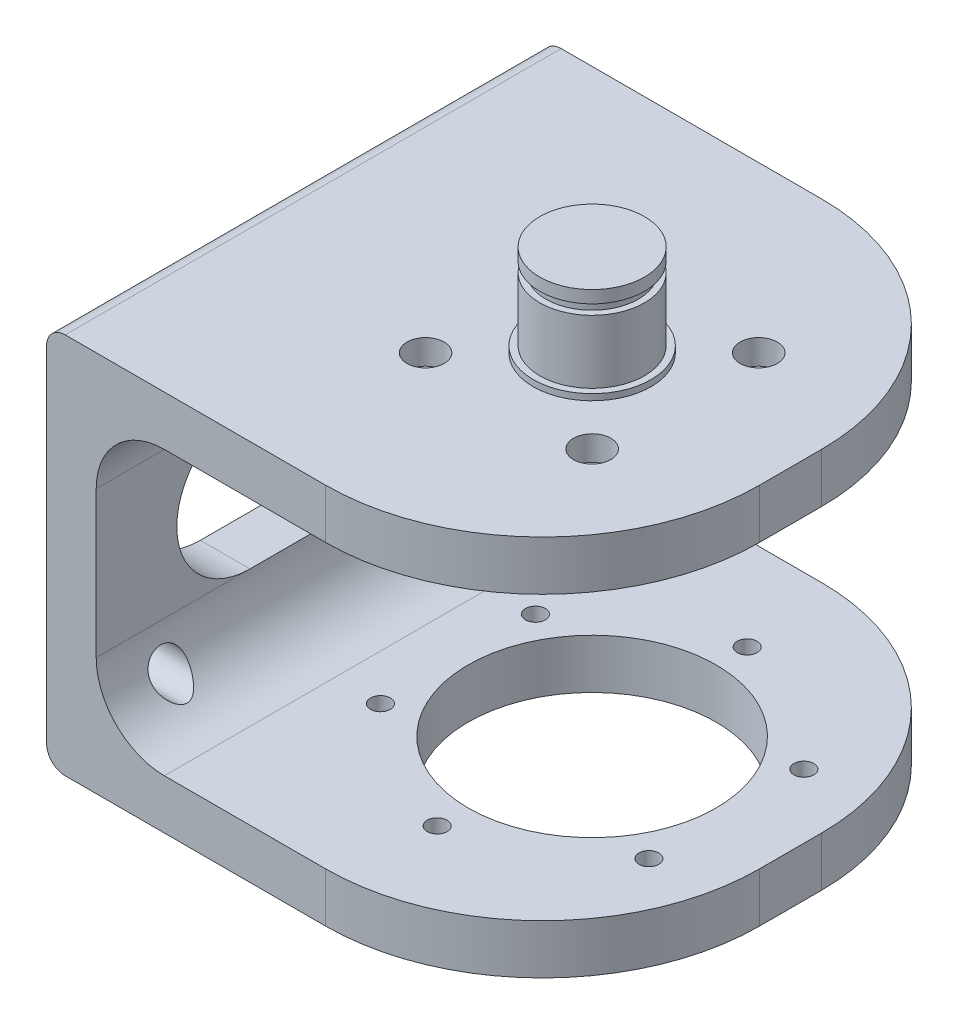
SolidWorks part; units mm, degrees
material "PETG-CF"
ref_plane "Front Plane" through (0, 0, 0) normal (0, 0, 1) x (1, 0, 0)
ref_plane "Top Plane" through (0, 0, 0) normal (0, 1, 0) x (1, 0, 0)
ref_plane "Right Plane" through (0, 0, 0) normal (1, 0, 0) x (0, 0, -1)
sketch "草图1" plane through (0, 0, 0) normal (0, 1, 0) x (1, 0, 0)
  line L1 (40, -40) -> (-40, -40)
  line L2 (40, -40) -> (40, 40)
  line L3 (40, 40) -> (-40, 40)
  line L4 (-40, -40) -> (-40, 40)
  line L5 (40, -40) -> (-40, 40) construction
  line L6 (40, 40) -> (-40, -40) construction
  point P0 (0, 0)
  dimension "D1" = 80
  dimension "D2" = 80
extrude "凸台-拉伸1" add sketch "草图1" along normal blind 8
sketch "草图2" plane through (0, 8, 0) normal (0, 1, 0) x (1, 0, 0)
  line L0 (-40, -40) -> (40, -40) construction
  line L1 (-32, -40) -> (-40, -40)
  line L2 (-32, -40) -> (-32, 40)
  line L3 (-32, 40) -> (-40, 40)
  line L4 (-40, -40) -> (-40, 40)
  line L5 (-32, -40) -> (-40, 40) construction
  line L6 (-32, 40) -> (-40, -40) construction
  point P0 (-36, 0)
  dimension "D1" = 8
extrude "凸台-拉伸2" add sketch "草图2" along normal blind 53.6
sketch "草图5" plane through (-32, 0, 0) normal (1, 0, 0) x (0, 0, -1)
  line L0 (-40, 61.6) -> (-40, 8) construction
  line L1 (40, 53.6) -> (-40, 53.6)
  line L2 (40, 53.6) -> (40, 61.6)
  line L3 (40, 61.6) -> (-40, 61.6)
  line L4 (-40, 53.6) -> (-40, 61.6)
  line L5 (40, 53.6) -> (-40, 61.6) construction
  line L6 (40, 61.6) -> (-40, 53.6) construction
  line L7 (40, 61.6) -> (40, 8) construction
  line L9 (-40, 61.6) -> (40, 61.6) construction
  point P0 (0, 57.6)
  dimension "D1" = 8
extrude "凸台-拉伸3" add sketch "草图5" along normal through all
sketch "草图4" plane through (0, 8, 0) normal (0, 1, 0) x (1, 0, 0)
  line L0 (-40, 40) -> (-40, -40) construction
  line L2 (40, -40) -> (40, 40) construction
  circle A0 centre (8, 0) radius 25 construction
  circle A1 centre (8, 25) radius 1.6
  circle A2 centre (-13.6506, 12.5) radius 1.6
  circle A3 centre (-13.6506, -12.5) radius 1.6
  circle A4 centre (8, -25) radius 1.6
  circle A5 centre (8, 0) radius 20
  circle A6 centre (29.6506, -12.5) radius 1.6
  circle A7 centre (29.6506, 12.5) radius 1.6
  point P17 (8, 0)
  point P22 (-40, 0)
  dimension "D3" = 50
  dimension "D4" = 3.2
  dimension "D6" = 40
  dimension "D1" = 32
  dimension "D5" = 6
extrude "切除-拉伸1" cut sketch "草图4" against normal through all contours A5 | A2 | A1 | A4 | A3 | A7 | A6
sketch "草图7" plane through (0, 61.6, 0) normal (0, 1, 0) x (1, 0, 0)
  line L0 (40, 40) -> (40, -40) construction
  line L3 (8, 0) -> (-5.435, 13.435) construction
  line L4 (8, 0) -> (8, 19) construction
  circle A0 centre (8, 0) radius 19 construction
  circle A5 centre (-5.435, 13.435) radius 1.6
  circle A6 centre (21.435, 13.435) radius 1.6
  circle A7 centre (21.435, -13.435) radius 1.6
  circle A8 centre (-5.435, -13.435) radius 1.6
  point P2 (5, 0)
  point P5 (5, 0)
  point P6 (10.7834, -6.382)
  point P10 (40, 0)
  point P20 (8, 0)
  dimension "D1" = 38
  dimension "D4" = 45
  dimension "D5" = 3.2
  dimension "D6" = 4
extrude "切除-拉伸3" cut sketch "草图7" against normal up to next
fillet "圆角3" radius 35 4 edges at (40, 4, 40) (40, 4, -40) (40, 57.6, -40) (40, 57.6, 40)
fillet "圆角4" radius 11 2 edges at (-32, 8, 0) (-32, 53.6, 0)
fillet "圆角5" radius 3 2 edges at (-40, 0, 0) (-40, 61.6, 0)
sketch "草图6" plane through (-40, 0, 0) normal (-1, 0, 0) x (0, 0, 1)
  line L0 (-40, 61.6) -> (40, 61.6) construction
  line L1 (30, 13) -> (-30, 13) construction
  line L2 (30, 13) -> (30, 48.6) construction
  line L3 (30, 48.6) -> (-30, 48.6) construction
  line L4 (-30, 13) -> (-30, 48.6) construction
  line L5 (30, 13) -> (-30, 48.6) construction
  line L6 (30, 48.6) -> (-30, 13) construction
  line L7 (40, 0) -> (-40, 0) construction
  line L8 (40, 58.6) -> (40, 3) construction
  line L9 (-40, 58.6) -> (-40, 3) construction
  line L10 (-30, 30.8) -> (30, 30.8) construction
  line L11 (0, 13) -> (0, 48.6) construction
  circle A0 centre (-30, 48.6) radius 1.6
  circle A1 centre (30, 48.6) radius 1.6
  circle A2 centre (30, 13) radius 1.6
  circle A3 centre (-30, 13) radius 1.6
  point P0 (0, 30.8)
  dimension "D5" = 3.2
  dimension "D1" = 13
  dimension "D2" = 13
  dimension "D3" = 10
  dimension "D4" = 10
extrude "切除-拉伸2" cut sketch "草图6" against normal through all
sketch "草图8" plane through (0, 61.6, 0) normal (0, 1, 0) x (1, 0, 0)
  circle A0 centre (8, 0) radius 8.45
  dimension "D1" = 16.9
extrude "凸台-拉伸4" add sketch "草图8" along normal blind 14.8
ref_plane "基准面1" through (0, 74.4, 0) normal (0, 1, 0) x (1, 0, 0)
sketch "草图10" plane through (0, 74.4, 0) normal (0, 1, 0) x (1, 0, 0)
  circle A0 centre (8, 0) radius 8.45
  circle A1 centre (8, 0) radius 7.45
  dimension "D1" = 14.9
extrude "切除-拉伸4" cut sketch "草图10" against normal blind 1.6
ref_plane "基准面2" through (-36, 0, 0) normal (-1, 0, 0) x (0, 0, 1)
sketch "草图12" plane through (-36, 0, 0) normal (-1, 0, 0) x (0, 0, 1)
  line L0 (-40, 30.8) -> (40, 30.8) construction
  line L1 (-40, 58.6) -> (-40, 3) construction
  line L2 (40, 58.6) -> (40, 3) construction
  line L3 (0, 61.6) -> (0, 3) construction
  line L4 (8.45, 61.6) -> (-8.45, 61.6) construction
  line L5 (-40, 3) -> (40, 3) construction
  circle A0 centre (-30, 48.6) radius 3
  circle A1 centre (30, 48.6) radius 3
  circle A2 centre (30, 13) radius 3
  circle A3 centre (-30, 13) radius 3
  dimension "D1" = 6
extrude "切除-拉伸5" cut sketch "草图12" against normal up to next
sketch "草图14" plane through (0, 61.6, 0) normal (0, 1, 0) x (1, 0, 0)
  circle A0 centre (-5.435, 13.435) radius 3
  circle A1 centre (21.435, 13.435) radius 3
  circle A2 centre (21.435, -13.435) radius 3
  circle A3 centre (-5.435, -13.435) radius 3
  point P12 (8, 0)
  dimension "D1" = 6
  dimension "D2" = 4
sketch "Sketch1" plane through (-32, 0, 0) normal (1, 0, 0) x (0, 0, -1)
  line L0 (15.2, 30.8) -> (-15.2, 30.8) construction
  line L1 (15.2, 19) -> (-15.2, 19)
  line L2 (15.2, 42.6) -> (-15.2, 42.6)
  line L3 (40, 42.6) -> (40, 19) construction
  line L4 (5, 61.6) -> (-5, 61.6) construction
  line L5 (40, 42.6) -> (-40, 42.6) construction
  arc A0 (15.2, 19) -> (15.2, 42.6) centre (15.2, 30.8) ccw
  arc A1 (-15.2, 42.6) -> (-15.2, 19) centre (-15.2, 30.8) ccw
  point P2 (0, 30.8)
  point P12 (40, 30.8)
  point P15 (0, 61.6)
  point P18 (27, 30.8)
  dimension "D1" = 13
extrude "Cut-Extrude1" cut sketch "Sketch1" against normal through all
extrude "切除-拉伸6" cut sketch "草图14" against normal blind 4
sketch "草图15" plane through (0, 0, 0) normal (0, -1, 0) x (1, 0, 0)
  circle A0 centre (-13.6506, 12.5) radius 3
  circle A1 centre (8, 25) radius 3
  circle A2 centre (29.6506, 12.5) radius 3
  circle A3 centre (29.6506, -12.5) radius 3
  circle A4 centre (8, -25) radius 3
  circle A5 centre (-13.6506, -12.5) radius 3
  point P15 (8, 0)
  dimension "D1" = 6
  dimension "D2" = 6
extrude "切除-拉伸7" cut sketch "草图15" against normal blind 4
sketch "草图16" plane through (0, 61.6, 0) normal (0, 1, 0) x (1, 0, 0)
  circle A0 centre (8, 0) radius 9.5
  dimension "D1" = 19
extrude "凸台-拉伸5" add sketch "草图16" along normal blind 1
